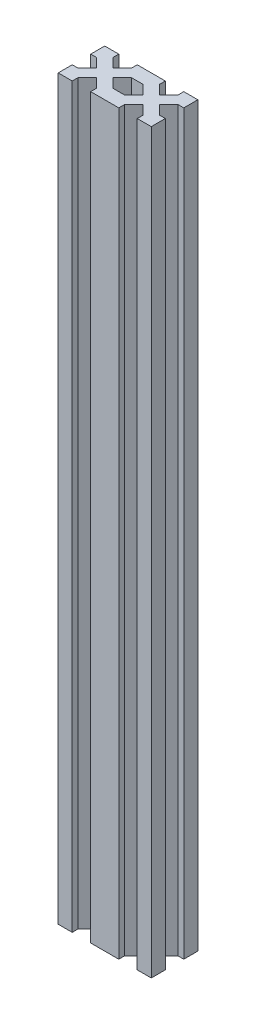
SolidWorks part; units mm, degrees
ref_plane "Plan de face" through (0, 0, 0) normal (0, 0, 1) x (1, 0, 0)
ref_plane "Plan de dessus" through (0, 0, 0) normal (0, 1, 0) x (1, 0, 0)
ref_plane "Plan de droite" through (0, 0, 0) normal (1, 0, 0) x (0, 0, -1)
sketch "Esquisse1" plane through (0, 0, 0) normal (0, 1, 0) x (1, 0, 0)
  line L0 (-2.5, 17.5) -> (-17.5, 17.5)
  line L1 (0, 0) -> (-20, 0)
  line L2 (0, 0) -> (0, 20)
  line L3 (0, 20) -> (-20, 20)
  line L4 (-20, 0) -> (-20, 20)
  line L5 (0, 20) -> (-20, 0) construction
  line L6 (-17.5, 2.5) -> (-17.5, 17.5)
  line L11 (-2.5, 2.5) -> (-17.5, 2.5)
  line L12 (-2.5, 2.5) -> (-2.5, 17.5)
  line L13 (-20, 20) -> (0, 0) construction
  line L14 (-26.9957, 23.4601) -> (-23.4601, 26.9957)
  line L15 (-26.9957, 23.4601) -> (3.4601, -6.9957)
  line L16 (-23.4601, 26.9957) -> (6.9957, -3.4601)
  line L17 (3.4601, -6.9957) -> (6.9957, -3.4601)
  line L18 (-26.9957, 23.4601) -> (6.9957, -3.4601) construction
  line L19 (-23.4601, 26.9957) -> (3.4601, -6.9957) construction
  line L20 (-10, 20) -> (-10, 0) construction
  line L21 (-23.4601, -6.9957) -> (-26.9957, -3.4601)
  line L22 (3.4601, 26.9957) -> (-26.9957, -3.4601)
  line L23 (6.9957, 23.4601) -> (-23.4601, -6.9957)
  line L24 (6.9957, 23.4601) -> (3.4601, 26.9957)
  line L25 (-17.5, 13.9645) -> (-20, 13.9645)
  line L26 (-20, 10) -> (20, 10) construction
  line L27 (-17.5, 6.0355) -> (-20, 6.0355)
  line L28 (-2.5, 6.0355) -> (2.5, 6.0355)
  line L29 (-2.5, 13.9645) -> (2.5, 13.9645)
  line L30 (-2.5, 6.0355) -> (2.5, 6.0355)
  line L31 (-2.5, 13.9645) -> (2.5, 13.9645)
  line L32 (-13.9645, 2.5) -> (-13.9645, 0)
  line L33 (-6.0355, 17.5) -> (-6.0355, 20)
  line L34 (-13.9645, 17.5) -> (-13.9645, 20)
  line L35 (-6.0355, 2.5) -> (-6.0355, 0)
  line L36 (0, 20) -> (0, -49980) construction
  line L37 (6.0355, 2.5) -> (6.0355, 0)
  line L38 (13.9645, 2.5) -> (13.9645, 0)
  line L39 (10, 20) -> (10, 0) construction
  line L40 (23.4601, 26.9957) -> (-3.4601, -6.9957) construction
  line L41 (26.9957, 23.4601) -> (-6.9957, -3.4601) construction
  line L42 (20, 20) -> (0, 0) construction
  line L43 (0, 20) -> (20, 0) construction
  line L44 (13.9645, 17.5) -> (13.9645, 20)
  line L45 (6.0355, 17.5) -> (6.0355, 20)
  line L46 (17.5, 6.0355) -> (20, 6.0355)
  line L47 (17.5, 13.9645) -> (20, 13.9645)
  line L48 (-6.9957, 23.4601) -> (-3.4601, 26.9957)
  line L49 (-6.9957, 23.4601) -> (23.4601, -6.9957)
  line L50 (-3.4601, 26.9957) -> (26.9957, -3.4601)
  line L51 (23.4601, -6.9957) -> (26.9957, -3.4601)
  line L52 (-3.4601, -6.9957) -> (-6.9957, -3.4601)
  line L53 (23.4601, 26.9957) -> (-6.9957, -3.4601)
  line L54 (26.9957, 23.4601) -> (-3.4601, -6.9957)
  line L55 (26.9957, 23.4601) -> (23.4601, 26.9957)
  line L56 (2.5, 2.5) -> (2.5, 17.5)
  line L57 (2.5, 2.5) -> (17.5, 2.5)
  line L58 (17.5, 2.5) -> (17.5, 17.5)
  line L59 (20, 0) -> (20, 20)
  line L60 (0, 20) -> (20, 20)
  line L61 (0, 0) -> (0, 20)
  line L62 (0, 0) -> (20, 0)
  line L63 (2.5, 17.5) -> (17.5, 17.5)
  point P11 (-10, 10)
  point P44 (0, 6.0355)
  point P45 (0, 10)
  point P59 (0, 13.9645)
  point P68 (10, 10)
  dimension "D1" = 20
  dimension "D2" = 20
  dimension "D3" = 7.3934
  dimension "D4" = 2.5
  dimension "D5" = 43.071
  dimension "D6" = 2.5
extrude "Boss.-Extru.1" [suppressed] add sketch "Esquisse1" along normal blind 340 contours L15 L35 L1 | L16 L12 L11 L15 L1 L2 | L28 L16 L2 | L16 L23 L15 L11 L12 | L32 L23 L1 | L23 L11 L6 L22 L4 L1 | L22 L27 L4 | L23 L15 L22 L6 L11 | L23 L16 L22 L15 | L23 L12 L0 L22 L16 | L23 L2 L3 L22 L0 L12 | L23 L29 L2 | L33 L22 L3 | L16 L34 L3 | L16 L3 L4 L15 L6 L0 | L25 L15 L4 | L22 L16 L0 L6 L15
extrude "Boss.-Extru.2" add sketch "Esquisse1<3>" along normal blind 316.8 contours L49 L62 L59 L50 L58 L57 | L38 L62 L49 | L50 L59 L46 | L60 L44 L53 | L47 L59 L54 | L53 L63 L58 L54 L59 L60 | L57 L58 L50 L54 L49 | L54 L50 L53 L49 | L63 L53 L50 L54 L58 | L56 L57 L54 L49 L53 | L57 L56 L53 L16 L54 | L2 L62 L16 | L2 L53 L1 | L53 L16 L12 L11 L15 | L28 L16 L2 | L53 L28 L2 | L15 L35 L1 | L54 L62 L37 | L16 L23 L15 L11 L12 | L23 L29 L2 | L49 L2 L29 | L56 L63 L50 L23 L49 | L60 L50 L45 | L60 L2 L23 | L49 L22 L0 L12 L23 | L3 L49 L2 | L33 L22 L3 | L23 L12 L0 L22 L16 | L23 L16 L22 L15 | L16 L34 L3 | L16 L3 L4 L15 L6 L0 | L25 L15 L4 | L22 L16 L0 L6 L15 | L22 L27 L4 | L32 L23 L1 | L23 L11 L6 L22 L4 L1 | L23 L15 L22 L6 L11 | L63 L56 L49 L53 L50 region at (-5.7812, 0, -14.2188) region at (-4.2678, 0, -17.5854) region at (-5.2022, 0, -19.1667) region at (-0.8333, 0, -14.7978) region at (-14.2188, 0, -14.2188) region at (-17.8661, 0, -17.8661) region at (-14.7978, 0, -19.1667) region at (-1.1785, 0, -18.8215) region at (-10, 0, -10) region at (-1.3104, 0, -4.7252) region at (-5.7812, 0, -5.7812) region at (-0.8333, 0, -5.2022) region at (0.8333, 0, -14.7978) region at (1.1785, 0, -18.8215) region at (1.8281, 0, -18.1719) region at (-14.2188, 0, -5.7812) region at (1.1785, 0, -1.1785) region at (1.3104, 0, -4.7252) region at (0.8333, 0, -5.2022) region at (-1.1785, 0, -1.1785) region at (5.2022, 0, -19.1667) region at (5.7812, 0, -14.2188) region at (-19.1667, 0, -14.7978) region at (-17.8661, 0, -2.1339) region at (-19.1667, 0, -5.2022) region at (-5.2022, 0, -0.8333) region at (5.2022, 0, -0.8333) region at (5.7812, 0, -5.7812) region at (10, 0, -10) region at (-14.7978, 0, -0.8333) region at (14.2188, 0, -14.2188) region at (14.7978, 0, -19.1667) region at (17.8661, 0, -17.8661) region at (14.2188, 0, -5.7812) region at (14.7978, 0, -0.8333) region at (17.8661, 0, -2.1339) region at (19.1667, 0, -5.2022) region at (19.1667, 0, -14.7978)
sketch "Esquisse1<3>" plane through (0, 0, 0) normal (0, 1, 0) x (1, 0, 0) same geometry as "Esquisse1"
